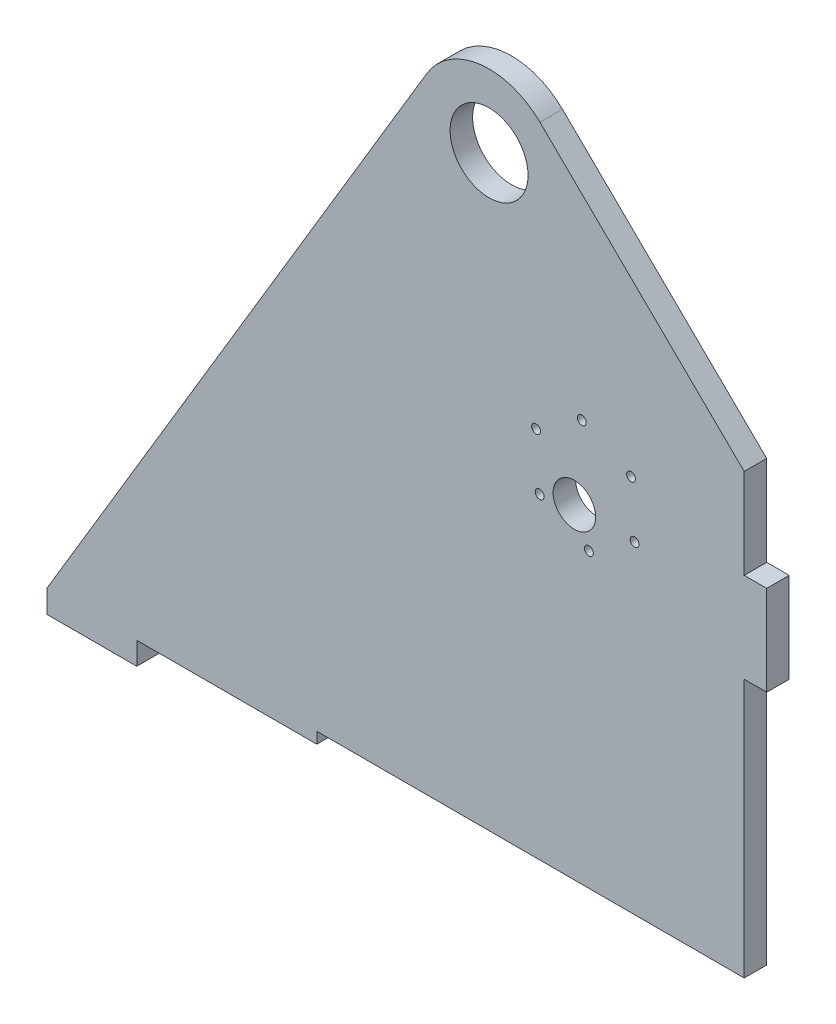
SolidWorks part; units mm, degrees
ref_plane "Front Plane" through (0, 0, 0) normal (0, 0, 1) x (1, 0, 0)
ref_plane "Top Plane" through (0, 0, 0) normal (0, 1, 0) x (1, 0, 0)
ref_plane "Right Plane" through (0, 0, 0) normal (1, 0, 0) x (0, 0, -1)
sketch "Sketch2" plane through (0, 0, 0) normal (0, 0, 1) x (1, 0, 0)
  line L1 (25.4, 6.35) -> (76.2, 6.35)
  line L2 (0, 6.35) -> (107.2144, 185.7594)
  line L4 (76.2, 6.35) -> (76.2, 9.525)
  line L6 (0, 6.35) -> (0, 0)
  line L7 (0, 0) -> (25.4, 0)
  line L8 (25.4, 6.35) -> (25.4, 0)
  line L13 (76.2, 9.525) -> (83.9864, 9.525)
  line L17 (0, -29.7981) -> (203.2, -29.7981) construction
  line L20 (196.85, 9.525) -> (196.85, 82.55)
  line L22 (196.85, 133.35) -> (139.2046, 189.8844)
  line L23 (196.85, 107.95) -> (196.85, 133.35)
  line L24 (196.85, 107.95) -> (203.2, 107.95)
  line L26 (196.85, 82.55) -> (203.2, 82.55)
  line L27 (203.2, 107.95) -> (203.2, 82.55)
  line L28 (83.9864, 9.525) -> (196.85, 9.525)
  arc A0 (139.2046, 189.8844) -> (107.2144, 185.7594) centre (124.8331, 175.2305) ccw
  circle A1 centre (124.8331, 175.2305) radius 11 construction
  circle A2 centre (124.8331, 175.2305) radius 4 construction
  circle A3 centre (124.8331, 175.2305) radius 11
  point P1 (0, 0)
  point P5 (83.9864, 9.525)
  dimension "D3" = 22
  dimension "D4" = 9.525
  dimension "D5" = 8
  dimension "D6" = 22
  dimension "D1" = 168.8805
  dimension "D2" = 124.8331
  dimension "D7" = 6.35
  dimension "D8" = 25.4
  dimension "D9" = 3.175
  dimension "D10" = 6.35
  dimension "D11" = 73.025
  dimension "D12" = 203.2
  dimension "D13" = 76.2
  dimension "D14" = 6.35
  dimension "D16" = 6.35
  dimension "D17" = 25.4
  dimension "D18" = 25.4
extrude "Boss-Extrude1" add sketch "Sketch2" along normal blind 6.35
sketch "Sketch4" [suppressed] plane through (0, 0, 6.35) normal (0, 0, 1) x (1, 0, 0)
  line L0 (1673.3123, 156.2334) -> (1577.5737, -3.9728)
  line L1 (1691.5051, 171.4226) -> (1750.822, 113.2489)
  line L2 (1684.7881, 175.4367) -> (1577.5737, -3.9728) construction
  line L3 (1590.9538, 18.4171) -> (1750.822, 18.4171)
  line L4 (1686.3016, 73.3904) -> (1617.2071, 143.6449) construction
  line L7 (1681.7742, 68.9378) -> (1612.6797, 139.1923)
  line L10 (1690.8289, 77.843) -> (1621.7344, 148.0975)
  line L13 (1566.672, 2.5421) -> (1566.672, -3.8079)
  line L14 (1566.672, -3.8079) -> (1592.072, -3.8079)
  line L15 (1592.072, -3.8079) -> (1592.072, 2.5421)
  line L16 (1592.072, 2.5421) -> (1642.872, 2.5421)
  line L17 (1642.872, 2.5421) -> (1642.872, 5.7171)
  line L18 (1642.872, 5.7171) -> (1763.522, 5.7171)
  line L24 (1763.522, 5.7171) -> (1763.522, 78.7421)
  line L25 (1673.8864, 181.9515) -> (1566.672, 2.5421)
  line L26 (1566.672, 2.5421) -> (1566.672, -3.8079)
  line L27 (1566.672, -3.8079) -> (1592.072, -3.8079)
  line L28 (1592.072, -3.8079) -> (1592.072, 2.5421)
  line L29 (1592.072, 2.5421) -> (1642.872, 2.5421)
  line L30 (1642.872, 2.5421) -> (1642.872, 5.7171)
  line L31 (1642.872, 5.7171) -> (1763.522, 5.7171)
  line L38 (1673.8864, 181.9515) -> (1566.672, 2.5421)
  line L39 (1686.3016, 73.3904) -> (1776.688, 147.3217) construction
  line L42 (1682.2812, 78.3056) -> (1772.6676, 152.2368)
  line L45 (1690.3219, 68.4752) -> (1780.7084, 142.4065)
  line L46 (1686.3016, 73.3904) -> (1535.3984, -21.6576) construction
  line L47 (1750.822, 113.2489) -> (1750.822, 18.4171)
  line L48 (1689.6858, 68.0174) -> (1538.7827, -27.0307)
  line L49 (1682.9173, 78.7634) -> (1532.0142, -16.2846)
  line L50 (1686.3016, 73.3904) -> (1767.8024, 12.8123) construction
  line L51 (1690.0896, 78.4868) -> (1771.5905, 17.9087)
  line L52 (1682.5135, 68.294) -> (1764.0144, 7.7159)
  line L53 (1691.5051, 171.4226) -> (1681.8948, -9.6316) construction
  line L54 (1697.8462, 171.086) -> (1688.2358, -9.9682)
  line L55 (1685.1641, 171.7592) -> (1675.5537, -9.2951)
  line L60 (1763.522, 5.7171) -> (1763.522, 78.7421)
  line L61 (1763.522, 129.5421) -> (1705.8766, 186.0765)
  line L62 (1763.522, 129.5421) -> (1705.8766, 186.0765)
  line L68 (1763.522, 78.7421) -> (1769.872, 78.7421)
  line L69 (1763.522, 78.7421) -> (1769.872, 78.7421)
  line L70 (1769.872, 78.7421) -> (1769.872, 104.1421)
  line L71 (1769.872, 78.7421) -> (1769.872, 104.1421)
  line L72 (1769.872, 104.1421) -> (1763.522, 104.1421)
  line L73 (1769.872, 104.1421) -> (1763.522, 104.1421)
  line L74 (1763.522, 104.1421) -> (1763.522, 129.5421)
  line L75 (1763.522, 104.1421) -> (1763.522, 129.5421)
  arc A1 (1705.8766, 186.0765) -> (1673.8864, 181.9515) centre (1691.5051, 171.4226) ccw
  arc A2 (1705.8766, 186.0765) -> (1673.8864, 181.9515) centre (1691.5051, 171.4226) ccw
  circle A4 centre (1691.5051, 171.4226) radius 23.7
  circle A5 centre (1691.5051, 171.4226) radius 23.7
  arc A14 (1681.7742, 68.9378) -> (1690.8289, 77.843) centre (1686.3016, 73.3904) ccw
  arc A15 (1621.7344, 148.0975) -> (1612.6797, 139.1923) centre (1617.2071, 143.6449) ccw
  arc A16 (1682.2812, 78.3056) -> (1690.3219, 68.4752) centre (1686.3016, 73.3904) ccw
  arc A17 (1780.7084, 142.4065) -> (1772.6676, 152.2368) centre (1776.688, 147.3217) ccw
  arc A18 (1689.6858, 68.0174) -> (1682.9173, 78.7634) centre (1686.3016, 73.3904) ccw
  arc A19 (1532.0142, -16.2846) -> (1538.7827, -27.0307) centre (1535.3984, -21.6576) ccw
  arc A20 (1690.0896, 78.4868) -> (1682.5135, 68.294) centre (1686.3016, 73.3904) ccw
  arc A21 (1764.0144, 7.7159) -> (1771.5905, 17.9087) centre (1767.8024, 12.8123) ccw
  arc A22 (1697.8462, 171.086) -> (1685.1641, 171.7592) centre (1691.5051, 171.4226) ccw
  arc A23 (1675.5537, -9.2951) -> (1688.2358, -9.9682) centre (1681.8948, -9.6316) ccw
  point P15 (1651.7543, 108.5176)
  point P28 (1731.4948, 110.356)
  point P35 (1610.85, 25.8664)
  point P42 (1727.052, 43.1013)
  point P50 (1686.6999, 80.8955)
  dimension "D6" = 6.35
  dimension "D4" = 12.7
  dimension "D5" = 12.7
  dimension "D1" = 0
  dimension "D2" = 12.7
  dimension "D3" = 12.7
extrude "Cut-Extrude1" [suppressed] cut sketch "Sketch4" against normal through all contours L49 L7 L0 | A5 L0 L10 L55 | A5 L54 L42 L1 | L45 L51 L47 L1 | L52 L54 L3 | L55 L48 L3
fillet "Fillet1" [suppressed] radius 2.54
sketch "Sketch5" plane through (0, 0, 0) normal (0, 0, -1) x (-1, 0, 0)
  circle A0 centre (-164.9005, 116.1111) radius 1.25 construction
  circle A2 centre (-165.9044, 100.6437) radius 1.25 construction
  circle A3 centre (-153.0111, 92.0405) radius 1.25 construction
  circle A4 centre (-151.0033, 122.9755) radius 1.25 construction
  circle A5 centre (-138.11, 114.3723) radius 1.25 construction
  circle A6 centre (-139.114, 98.9049) radius 1.25 construction
  circle A7 centre (-148.9072, 101.2319) radius 6
  circle A8 centre (-164.9005, 116.1111) radius 1.25
  circle A9 centre (-165.9044, 100.6437) radius 1.25
  circle A10 centre (-153.0111, 92.0405) radius 1.25
  circle A11 centre (-151.0033, 122.9755) radius 1.25
  circle A12 centre (-138.11, 114.3723) radius 1.25
  circle A13 centre (-139.114, 98.9049) radius 1.25
  point P0 (-149.665, 101.2319)
  dimension "D1" = 6
extrude "Cut-Extrude2" cut sketch "Sketch5" against normal through all both and the other way through all
